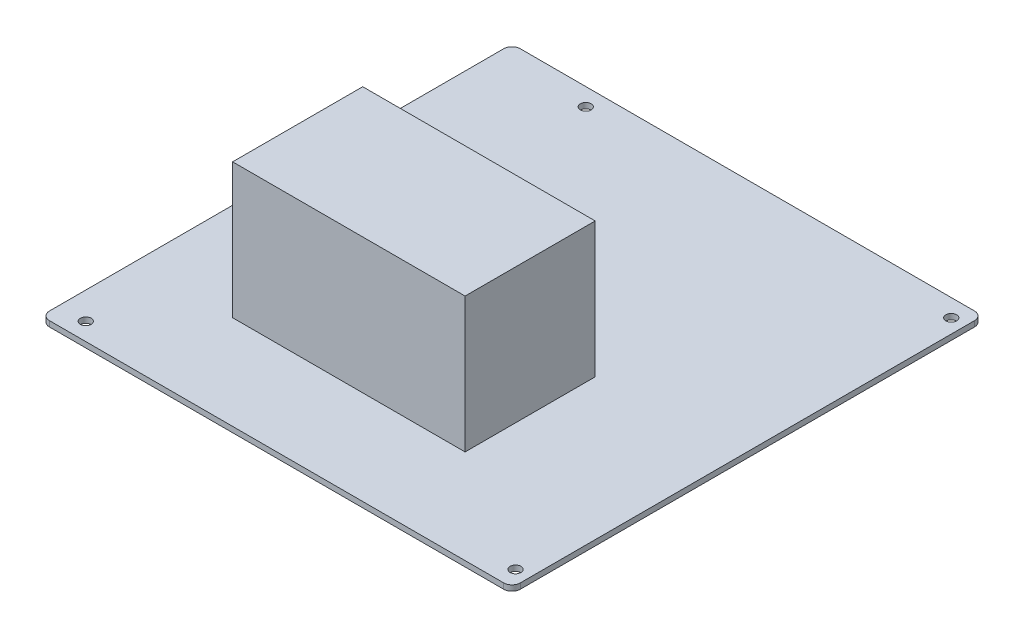
SolidWorks part; units mm, degrees
ref_plane "Front" through (0, 0, 0) normal (0, 0, 1) x (1, 0, 0)
ref_plane "Top" through (0, 0, 0) normal (0, 1, 0) x (1, 0, 0)
ref_plane "Right" through (0, 0, 0) normal (1, 0, 0) x (0, 0, -1)
sketch "Sketch1" plane through (0, 0, 0) normal (0, 1, 0) x (1, 0, 0)
  line L1 (85.09, 85.09) -> (-85.09, 85.09)
  line L2 (85.09, 85.09) -> (85.09, -85.09)
  line L3 (85.09, -85.09) -> (-85.09, -85.09)
  line L4 (-85.09, 85.09) -> (-85.09, -85.09)
  line L5 (85.09, 85.09) -> (-85.09, -85.09) construction
  line L6 (85.09, -85.09) -> (-85.09, 85.09) construction
  point P0 (0, 0)
  dimension "D1" = 170.18
  dimension "D2" = 170.18
extrude "Boss-Extrude1" add sketch "Sketch1" along normal blind 2
sketch "Sketch2" plane through (0, 2, 0) normal (0, 1, 0) x (1, 0, 0)
  line L1 (-49.8792, -4.0694) -> (34.1365, -4.0694)
  line L2 (-49.8792, -4.0694) -> (-49.8792, -51.0882)
  line L3 (-49.8792, -51.0882) -> (34.1365, -51.0882)
  line L4 (34.1365, -4.0694) -> (34.1365, -51.0882)
  line L5 (-49.8792, -4.0694) -> (34.1365, -51.0882) construction
  line L6 (-49.8792, -51.0882) -> (34.1365, -4.0694) construction
  point P0 (-7.8713, -27.5788)
  point P5 (34.1365, -51.0882)
  point P6 (-49.8792, -4.0694)
extrude "Boss-Extrude2" add sketch "Sketch2" along normal blind 48.8
fillet "Fillet1" radius 3 4 edges at (-85.09, 1, -85.09) (85.09, 1, -85.09) (85.09, 1, 85.09) (-85.09, 1, 85.09)
hole_wizard "Ø3.9 (3.9) Diameter Hole1" positions "Sketch3" profile "Sketch4" hole size "Ø3.9" standard "ANSI Metric"
sketch "Sketch3" plane through (0, 2, 0) normal (0, 1, 0) x (1, 0, 0)
  line L0 (-82.09, -85.09) -> (82.09, -85.09) construction
  line L1 (85.09, -82.09) -> (85.09, 82.09) construction
  line L3 (-52.07, 78.74) -> (80.01, 78.74) construction
  point P0 (-75.29, -78.74)
  point P2 (80.01, -78.74)
  point P4 (80.01, 78.74)
  point P6 (-52.07, 78.74)
  dimension "D1" = 6.35
  dimension "D2" = 6.35
  dimension "D3" = 5.08
  dimension "D4" = 5.08
  dimension "D5" = 157.48
  dimension "D6" = 132.08
  dimension "D7" = 155.3
sketch "Sketch4" plane through (-75.29, 2, 78.74) normal (1, 0, 0) x (0, 0, 1)
  line L0 (0, 0) -> (0, 19.9217)
  line L1 (0, 19.9217) -> (1.95, 18.75)
  line L2 (1.95, 18.75) -> (1.95, 0)
  line L5 (1.95, 0) -> (0, 0)
  line L10 (0, 19.9217) -> (-1.95, 18.75) construction
  line L11 (0, -6.35) -> (0, 107.95) construction
  dimension "Hole Dia." = 3.9
  dimension "Hole Depth" = 18.75
  dimension "Drill Angle" = 118
